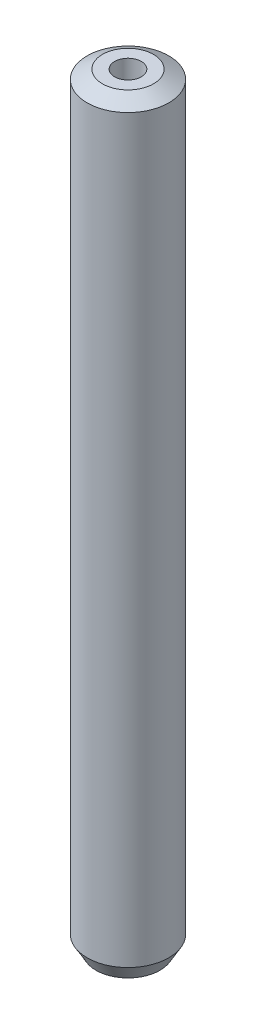
SolidWorks part; units mm, degrees
ref_plane "Front Plane" through (0, 0, 0) normal (0, 0, 1) x (1, 0, 0)
ref_plane "Top Plane" through (0, 0, 0) normal (0, 1, 0) x (1, 0, 0)
ref_plane "Right Plane" through (0, 0, 0) normal (1, 0, 0) x (0, 0, -1)
sketch "Sketch1" plane through (0, 0, 0) normal (0, 1, 0) x (1, 0, 0)
  circle A0 centre (0, 0) radius 25
  dimension "SHAFT_OD" = 50
extrude "Boss-Extrude1" add sketch "Sketch1" along normal blind 468.5098
sketch "Sketch2" plane through (0, 0, 0) normal (0, 1, 0) x (1, 0, 0)
  circle A0 centre (0, 0) radius 8.1838
  dimension "BORE_D" = 16.3675
extrude "Cut-Extrude1" cut sketch "Sketch2" along normal through all
chamfer "Chamfer1" distance 5.4043 angle 60 2 edges at (0, 468.5098, 25) (0, 0, 25) first distance on face at (0, 468.5098, 25) first distance on face at (0, 0, 8.1838)
